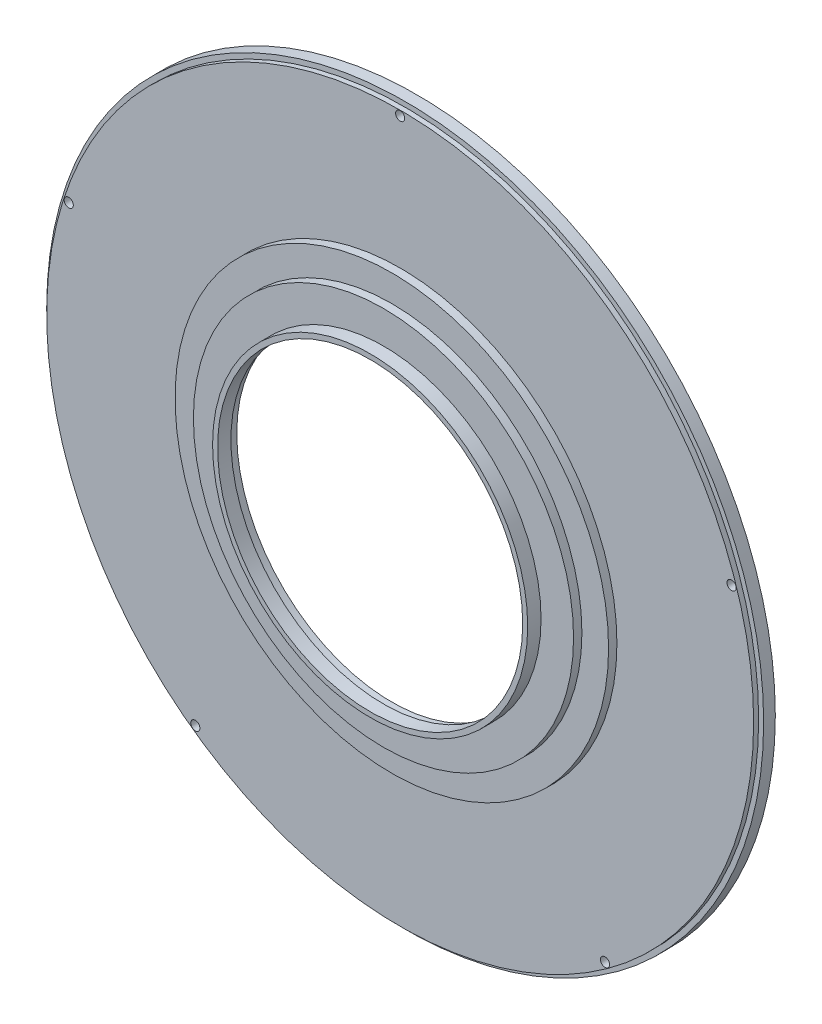
SolidWorks part; units mm, degrees
ref_plane "Front Plane" through (0, 0, 0) normal (0, 0, 1) x (1, 0, 0)
ref_plane "Top Plane" through (0, 0, 0) normal (0, 1, 0) x (1, 0, 0)
ref_plane "Right Plane" through (0, 0, 0) normal (1, 0, 0) x (0, 0, -1)
sketch "Sketch1" plane through (0, 0, 0) normal (0, 0, 1) x (1, 0, 0)
  circle A0 centre (0, 0) radius 215
  circle A1 centre (0, 0) radius 120
extrude "Plate" add sketch "Sketch1" along normal blind 10
ref_plane "Plane_z10" through (0, 0, 10) normal (0, 0, 1) x (1, 0, 0)
sketch "Sketch2" plane through (0, 0, 10) normal (0, 0, 1) x (1, 0, 0)
  circle A0 centre (0, 0) radius 130
  circle A1 centre (0, 0) radius 111
extrude "Bellmouth1" add sketch "Sketch2" along normal blind 5
ref_plane "Plane_z15" through (0, 0, 15) normal (0, 0, 1) x (1, 0, 0)
sketch "Sketch3" plane through (0, 0, 15) normal (0, 0, 1) x (1, 0, 0)
  circle A0 centre (0, 0) radius 114
  circle A1 centre (0, 0) radius 93
extrude "Bellmouth2" add sketch "Sketch3" along normal blind 5
ref_plane "Plane_z20" through (0, 0, 20) normal (0, 0, 1) x (1, 0, 0)
sketch "Sketch4" plane through (0, 0, 20) normal (0, 0, 1) x (1, 0, 0)
  circle A0 centre (0, 0) radius 94.5
  circle A1 centre (0, 0) radius 91.5
extrude "Bellmouth3" add sketch "Sketch4" along normal blind 8
sketch "Sketch5" plane through (0, 0, 0) normal (0, 0, 1) x (1, 0, 0)
  circle A0 centre (0, 0) radius 204
  circle A1 centre (0, 0) radius 144
extrude "Comb_groove" cut sketch "Sketch5" along normal blind 4
ref_plane "Plane_z7" through (0, 0, 7) normal (0, 0, 1) x (1, 0, 0)
sketch "Sketch6" plane through (0, 0, 7) normal (0, 0, 1) x (1, 0, 0)
  circle A0 centre (0, 0) radius 216
  circle A1 centre (0, 0) radius 212
extrude "Band_rabbet" cut sketch "Sketch6" along normal blind 3
sketch "Sketch7" plane through (0, 0, 0) normal (0, 0, 1) x (1, 0, 0)
  circle A0 centre (198.7708, 64.5846) radius 2.75
  circle A1 centre (0, 209) radius 2.75
  circle A2 centre (-198.7708, 64.5846) radius 2.75
  circle A3 centre (-122.8471, -169.0846) radius 2.75
  circle A4 centre (122.8471, -169.0846) radius 2.75
extrude "Rod_holes" cut sketch "Sketch7" along normal blind 10
